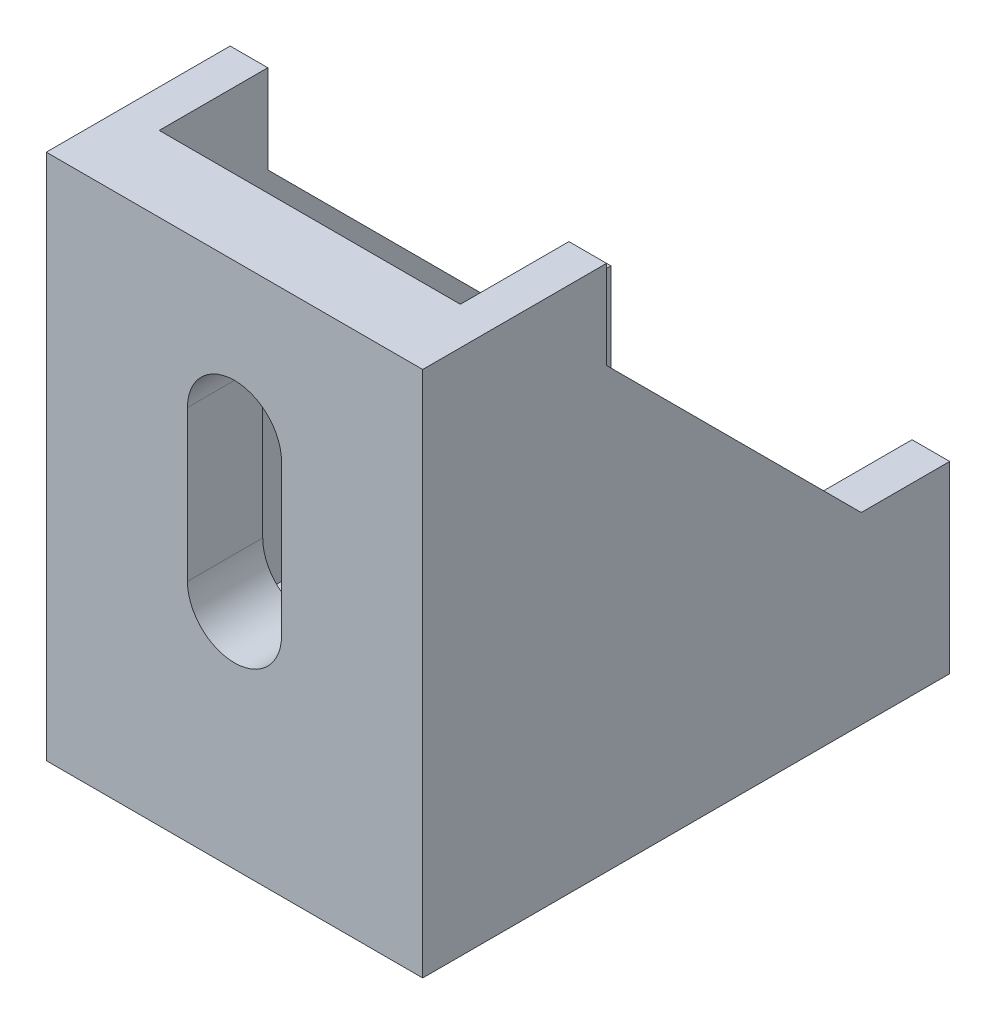
SolidWorks part; units mm, degrees
ref_plane "Front Plane" through (0, 0, 0) normal (0, 0, 1) x (1, 0, 0)
ref_plane "Top Plane" through (0, 0, 0) normal (0, 1, 0) x (1, 0, 0)
ref_plane "Right Plane" through (0, 0, 0) normal (1, 0, 0) x (0, 0, -1)
sketch "Sketch1" plane through (0, 0, 0) normal (1, 0, 0) x (0, 0, -1)
  line L0 (0, 0) -> (0, 28)
  line L1 (0, 28) -> (9.7688, 28)
  line L2 (4, 28) -> (4, 4)
  line L3 (28, 9.7688) -> (28, 0)
  line L4 (28, 0) -> (0, 0)
  line L5 (9.7688, 28) -> (9.7688, 23.2999)
  line L6 (9.7688, 23.2999) -> (23.2999, 9.7688)
  line L7 (23.2999, 9.7688) -> (28, 9.7688)
  line L8 (4, 4) -> (28, 4)
  dimension "D1" = 28
  dimension "D2" = 4
extrude "Boss-Extrude2" add sketch "Sketch1" along normal blind 20 contours L8 L2 L1 L0 L4 L3 region at (0, 14, -0.396)
extrude "Boss-Extrude3" add sketch "Sketch1<4>" along normal blind 2 contours L2 L8 L3 L7 L6 L5 L1 region at (0, 12.6696, -12.6696)
sketch "Sketch1<4>" plane through (0, 0, 0) normal (1, 0, 0) x (0, 0, -1) same geometry as "Sketch1"
extrude "Boss-Extrude4" add sketch "Sketch1<5>" against normal blind 2 from vertex contours L2 L8 L3 L7 L6 L5 L1 region at (0, 12.6696, -12.6696) starting at point (20, 4, -4)
sketch "Sketch1<5>" plane through (0, 0, 0) normal (1, 0, 0) x (0, 0, -1) same geometry as "Sketch1"
sketch "Sketch2" plane through (0, 4, 0) normal (0, 1, 0) x (1, 0, 0)
  line L0 (10, 12) -> (10, 20) construction
  line L1 (7.5, 12) -> (7.5, 20)
  line L2 (12.5, 12) -> (12.5, 20)
  line L3 (18, 4) -> (2, 4) construction
  line L5 (2, 4) -> (2, 28) construction
  arc A0 (7.5, 12) -> (12.5, 12) centre (10, 12) ccw
  arc A1 (12.5, 20) -> (7.5, 20) centre (10, 20) ccw
  point P2 (10, 16)
  point P10 (10, 4)
  point P17 (2, 16)
  dimension "D1" = 5
  dimension "D2" = 8
extrude "Cut-Extrude1" cut sketch "Sketch2" against normal through all
sketch "Sketch4" plane through (0, 0, -4) normal (0, 0, -1) x (-1, 0, 0)
  line L0 (-10, 12) -> (-10, 20) construction
  line L1 (-12.5, 12) -> (-12.5, 20)
  line L2 (-7.5, 12) -> (-7.5, 20)
  line L3 (-18, 4) -> (-2, 4) construction
  line L4 (-18, 28) -> (-18, 4) construction
  arc A0 (-12.5, 12) -> (-7.5, 12) centre (-10, 12) ccw
  arc A1 (-7.5, 20) -> (-12.5, 20) centre (-10, 20) ccw
  point P2 (-10, 16)
  point P12 (-10, 4)
  point P16 (-18, 16)
  dimension "D2" = 8
  dimension "D1" = 5
extrude "Cut-Extrude2" cut sketch "Sketch4" against normal through all contours L1 A1 L2 A0
